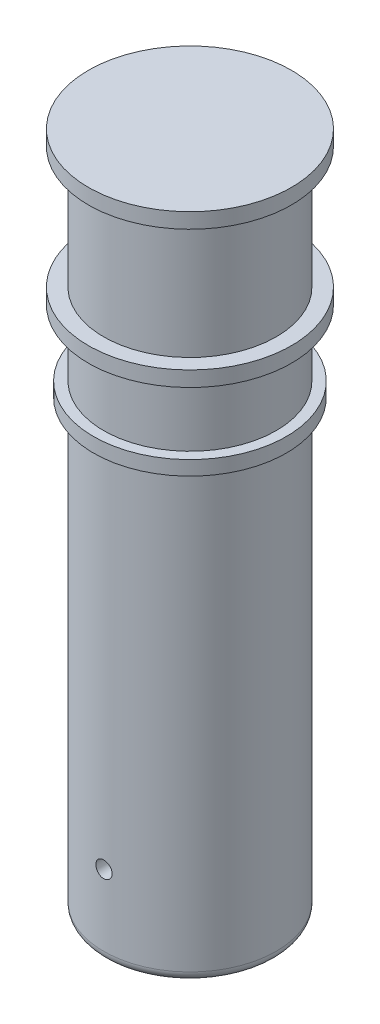
SolidWorks part; units mm, degrees
material "ABS"
ref_plane "Front Plane" through (0, 0, 0) normal (0, 0, 1) x (1, 0, 0)
ref_plane "Top Plane" through (0, 0, 0) normal (0, 1, 0) x (1, 0, 0)
ref_plane "Right Plane" through (0, 0, 0) normal (1, 0, 0) x (0, 0, -1)
sketch "Sketch1" plane through (0, 0, 0) normal (0, 0, 1) x (1, 0, 0)
  line L2 (-8.5, -51.915) -> (-8.5, -7.915)
  line L3 (-8.5, 0) -> (-10, 0)
  line L4 (-10, 0) -> (-10, 1.5)
  line L5 (-10, 1.5) -> (-8.5, 1.5)
  line L6 (-8.5, 1.5) -> (-8.5, 13.5)
  line L7 (-8.5, 13.5) -> (-10, 13.5)
  line L8 (-10, 13.5) -> (-10, 15)
  line L9 (-10, 15) -> (0, 15)
  line L10 (0, 15) -> (0, -37.915)
  line L11 (-4, -51.915) -> (-8.5, -51.915)
  line L12 (-4, -37.915) -> (-4, -51.915)
  line L13 (0, -37.915) -> (-4, -37.915)
  line L14 (-8.5, -7.915) -> (-9.5, -7.915)
  line L16 (-9.5, -7.915) -> (-9.5, -6.5)
  line L17 (-9.5, -6.5) -> (-8.5, -6.5)
  line L18 (-8.5, -6.5) -> (-8.5, 0)
  point P1 (-8.8902, 0)
  dimension "D1" = 8.5
  dimension "D2" = 1.5
  dimension "D3" = 51.915
  dimension "D4" = 1.5
  dimension "D5" = 4
  dimension "D6" = 14
  dimension "D7" = 15
  dimension "D8" = 10
  dimension "D9" = 44
  dimension "D10" = 1
  dimension "6.5" = 6.5
revolve "Revolve1" add sketch "Sketch1" angle 360 about L10
fillet "Fillet1" radius 1 2 edges at (-8.5, -51.915, 0) (-4, -51.915, 0)
hole_wizard "M2x0.4 Tapped Hole1" positions "Sketch2" profile "Sketch3" tap size "M2x0.4" standard "ANSI Metric" end condition up to next
sketch "Sketch2" plane through (0, 0, 0) normal (0, 0, 1) x (1, 0, 0)
  line L0 (-7.5, -51.915) -> (7.5, -51.915) construction
  point P0 (0, -43.915)
  dimension "D1" = 8
sketch "Sketch3" plane through (0, -43.915, 0) normal (1, 0, 0) x (0, 1, 0)
  line L0 (0, 0) -> (0, 8.5)
  line L1 (0, 8.5) -> (0.8, 8.5)
  line L2 (0.8, 8.5) -> (0.8, 0)
  line L5 (0.8, 0) -> (0, 0)
  line L11 (0, -6.35) -> (0, 107.95) construction
  dimension "Thru Tap Drill Dia." = 1.6
  dimension "Thru Tap Drill Depth" = 8.5
cosmetic thread "Hole Thread1" parameters "D2"=2
